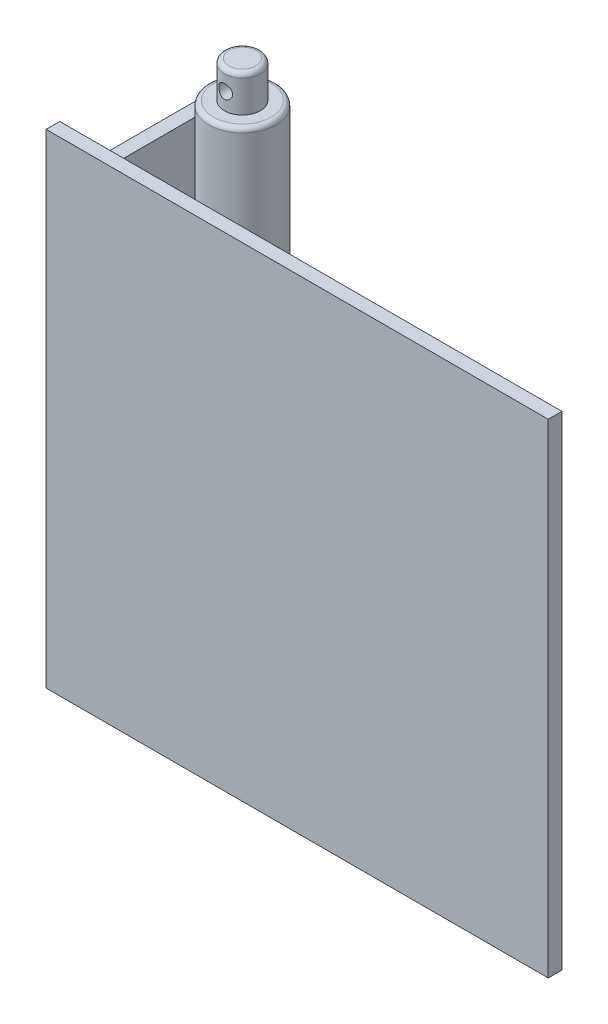
SolidWorks part; units mm, degrees
note: '?' marks a value the reader was unsure of.
ref_plane "前视基准面" through (0, 0, 0) normal (0, 0, 1) x (1, 0, 0)
ref_plane "上视基准面" through (0, 0, 0) normal (0, 1, 0) x (1, 0, 0)
ref_plane "右视基准面" through (0, 0, 0) normal (1, 0, 0) x (0, 0, -1)
other "Configuration Table"
sketch "草图1" plane through (0, 0, 0) normal (0, 0, 1) x (1, 0, 0)
  line L1 (0, -10) -> (110, -10)
  line L2 (0, -10) -> (0, 96)
  line L3 (0, 96) -> (110, 96)
  line L4 (110, -10) -> (110, 96)
  dimension "D1" = 110
  dimension "D2" = 106
extrude "凸台-拉伸1" add sketch "草图1" along normal blind 3
sketch "草图2" plane through (0, 0, 0) normal (0, 0, -1) x (-1, 0, 0)
  line L0 (-5, -4) -> (-8, -4)
  line L1 (0, 96) -> (0, -10) construction
  line L2 (-8, -4) -> (-8, 90)
  line L3 (-8, 90) -> (-5, 90)
  line L4 (-5, 90) -> (-5, -4)
  line L7 (0, 96) -> (-110, 96) construction
  line L8 (0, -10) -> (-110, -10) construction
  dimension "D1" = 3
  dimension "D2" = 6
  dimension "D3" = 6
  dimension "D4" = 5
extrude "凸台-拉伸2" add sketch "草图2" along normal blind 38
sketch "草图3" plane through (5, 0, 0) normal (-1, 0, 0) x (0, 0, 1)
  circle A0 centre (-33.6812, 43.141) radius 1.5
  circle A1 centre (-13.4256, 43.141) radius 1.5
  dimension "D1" = 3
  dimension "D2" = 3
sketch "草图4" plane through (0, 90, 0) normal (0, 1, 0) x (1, 0, 0)
  circle A2 centre (15, 25) radius 7.35
  dimension "D1" = 14.7
extrude "凸台-拉伸3" add sketch "草图4" against normal offset from surface 4 and the other way blind 5
sketch "草图5" plane through (0, 95, 0) normal (0, 1, 0) x (1, 0, 0)
  circle A0 centre (15, 25) radius 3.95
  dimension "D1" = 7.9
extrude "凸台-拉伸4" add sketch "草图5" along normal blind 8
fillet "圆角2" radius 1 2 edges at (15, 103, -21.05) (15, 95, -17.65)
ref_axis "基准轴2" through (15, 102, -25) along (0, -1, 0)?
ref_plane "基准面2" through (0, 0, -25) normal (0, 0, -1) x (-1, 0, 0)
sketch "草图7" plane through (0, 0, -25) normal (0, 0, -1) x (-1, 0, 0)
  spline S1 degree 3 poles (-12.382, 97.3906) (-12.382, 97.6094) (-12.3922, 97.7173) (-12.4329, 97.9301) (-12.4636, 98.035) (-12.5823, 98.3328) (-12.7002, 98.5161) (-12.9927, 98.8189) (-13.1703, 98.9416) (-13.462, 99.0655) (-13.5651, 99.0974) (-13.7733, 99.1395) (-13.8792, 99.1501) (-14.2024, 99.1499) (-14.4164, 99.1068) (-14.718, 98.9816) (-14.8132, 98.9307) (-14.993, 98.8113) (-15.0785, 98.7419) (-15.2326, 98.5896) (-15.3017, 98.5068) (-15.4238, 98.3275) (-15.4765, 98.2311) (-15.6027, 97.933) (-15.6472, 97.7151) (-15.6471, 97.3914) (-15.636, 97.2819) (-15.5924, 97.0696) (-15.5603, 96.9667) (-15.4758, 96.7675) (-15.4228, 96.6709) (-15.3012, 96.4926) (-15.2321, 96.4097) (-14.9993, 96.1802) (-14.8161, 96.0588) (-14.515, 95.9343) (-14.412, 95.903) (-14.2009, 95.8607) (-14.0919, 95.8499) (-13.7712, 95.8501) (-13.5574, 95.8939) (-13.17, 96.0587) (-12.9922, 96.1815) (-12.7727, 96.4089) (-12.7059, 96.4934) (-12.5909, 96.6725) (-12.5424, 96.7671) (-12.463, 96.9667) (-12.4325, 97.0717) (-12.3922, 97.2831) (-12.382, 97.3906) (-12.382, 97.6094) (-12.3922, 97.7173) knots -0.03125 -0.03125 0 0 0.03125 0.03125 0.0625 0.0625 0.125 0.125 0.1875 0.1875 0.21875 0.21875 0.25 0.25 0.3125 0.3125 0.34375 0.34375 0.375 0.375 0.40625 0.40625 0.4375 0.4375 0.5 0.5 0.53125 0.53125 0.5625 0.5625 0.59375 0.59375 0.625 0.625 0.6875 0.6875 0.71875 0.71875 0.75 0.75 0.8125 0.8125 0.875 0.875 0.90625 0.90625 0.9375 0.9375 0.96875 0.96875 1 1 1.03125 1.03125 1.0625 only from (-12.382, 97.5) to (-12.382, 97.5)
ref_plane "基准面3" through (0, 0, -28.95) normal (0, 0, -1) x (-1, 0, 0)
sketch "草图9" plane through (0, 0, -28.95) normal (0, 0, -1) x (-1, 0, 0)
  line L0 (-15, 102) -> (-15, 95) construction
  circle A0 centre (-15, 98.678) radius 1.5
  dimension "D1" = 3
extrude "切除-拉伸1" cut sketch "草图9" against normal through all both and the other way through all
fillet "圆角3" radius 0.5 1 edges at (15, -14.122, -17.65)
sketch "草图11" plane through (0, 0, -38) normal (0, 0, -1) x (-1, 0, 0)
  line L1 (-8, 90) -> (-5, 90)
  line L2 (-8, 90) -> (-8, -4)
  line L3 (-8, -4) -> (-5, -4)
  line L4 (-5, 90) -> (-5, -4)
extrude "切除-拉伸3" cut sketch "草图11" against normal blind 12
